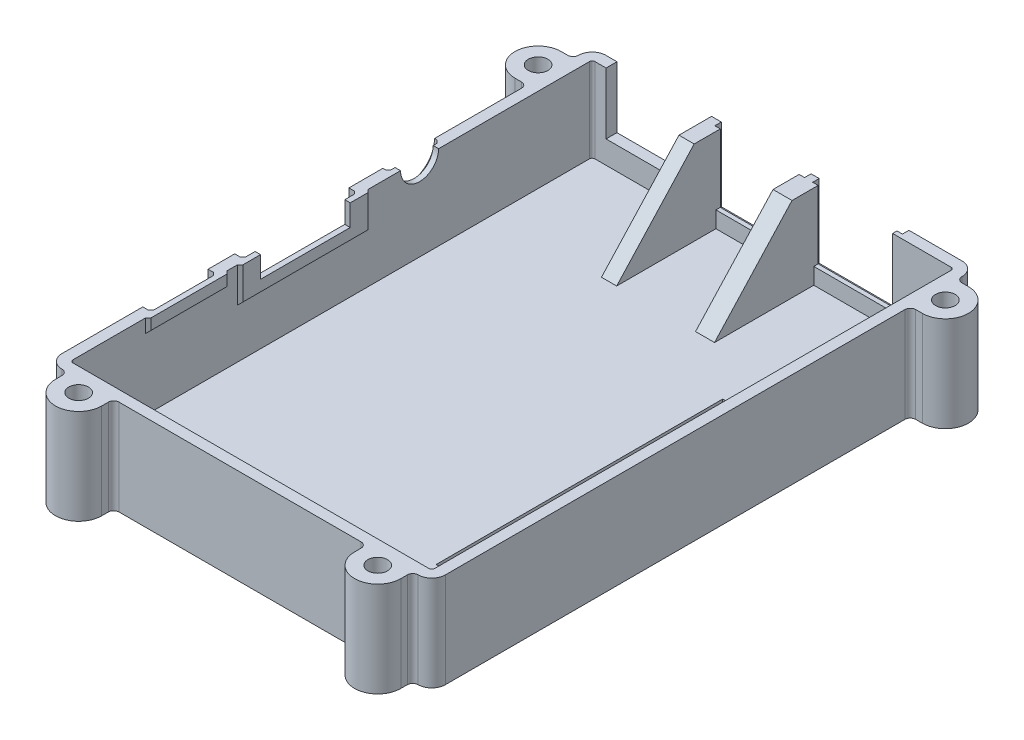
SolidWorks part; units mm, degrees
ref_plane "Front Plane" through (0, 0, 0) normal (0, 0, 1) x (1, 0, 0)
ref_plane "Top Plane" through (0, 0, 0) normal (0, 1, 0) x (1, 0, 0)
ref_plane "Right Plane" through (0, 0, 0) normal (1, 0, 0) x (0, 0, -1)
sketch "Sketch2" plane through (0, 0, 0) normal (0, 1, 0) x (1, 0, 0)
  line L1 (2.5, 0) -> (68, 0)
  line L2 (0, 2.5) -> (0, 97.5)
  line L3 (2.5, 100) -> (68, 100)
  line L4 (70.5, 2.5) -> (70.5, 97.5)
  arc A0 (0, 2.5) -> (2.5, 0) centre (2.5, 2.5) ccw
  arc A1 (68, 0) -> (70.5, 2.5) centre (68, 2.5) ccw
  arc A2 (70.5, 97.5) -> (68, 100) centre (68, 97.5) ccw
  arc A3 (2.5, 100) -> (0, 97.5) centre (2.5, 97.5) ccw
  point P7 (0, 0)
  point P10 (70.5, 0)
  point P13 (70.5, 100)
  point P16 (0, 100)
  dimension "D3" = 2.5
  dimension "D1" = 70.5
  dimension "D2" = 100
extrude "Base" add sketch "Sketch2" along normal blind 17.5
shell "Shell" thickness 2 removed face at (35.25, 17.5, -50)
sketch "Sketch14" plane through (0, 0, 0) normal (0, -1, 0) x (1, 0, 0)
  line L0 (35.25, 0) -> (35.25, -100) construction
  line L2 (68, -100) -> (2.5, -100) construction
  line L3 (-2.2, -88) -> (0, -88)
  line L4 (0, -97.5) -> (0, -2.5) construction
  line L5 (0, -88) -> (0, -96.5)
  line L6 (0, -96.5) -> (-2.2, -96.5)
  line L7 (3.5, 2.2) -> (3.5, 0)
  line L8 (2.5, 0) -> (68, 0) construction
  line L9 (3.5, 0) -> (12, 0)
  line L10 (12, 0) -> (12, 2.2)
  line L11 (72.7, -88) -> (70.5, -88)
  line L12 (70.5, -96.5) -> (72.7, -96.5)
  line L13 (70.5, -88) -> (70.5, -96.5)
  line L14 (58.5, 0) -> (58.5, 2.2)
  line L15 (67, 0) -> (58.5, 0)
  line L16 (67, 2.2) -> (67, 0)
  line L17 (2.5, 0) -> (68, 0) construction
  arc A0 (-2.2, -88) -> (-2.2, -96.5) centre (-2.2, -92.25) ccw
  arc A1 (3.5, 2.2) -> (12, 2.2) centre (7.75, 2.2) cw
  arc A2 (72.7, -88) -> (72.7, -96.5) centre (72.7, -92.25) cw
  arc A3 (67, 2.2) -> (58.5, 2.2) centre (62.75, 2.2) ccw
  dimension "D1" = 2.2
  dimension "D2" = 8.5
  dimension "D3" = 3.5
  dimension "D4" = 3.5
extrude "Clamps" add sketch "Sketch14" against normal up to surface (17.5 mm away) up to face at (35.25, 17.5, -50)
fillet "Clamp Fillets" radius 1 8 edges at (58.5, 8.75, 0) (67, 8.75, 0) (12, 8.75, 0) (3.5, 8.75, 0) (0, 8.75, -96.5) (0, 8.75, -88) (70.5, 8.75, -88) (70.5, 8.75, -96.5)
sketch "Sketch20" plane through (0, 0, 0) normal (0, -1, 0) x (1, 0, 0)
  circle A0 centre (7.75, 2.2) radius 1.8
  circle A1 centre (62.75, 2.2) radius 1.8
  circle A2 centre (72.7, -92.25) radius 1.8
  circle A3 centre (-2.2, -92.25) radius 1.8
  arc A4 (12, 2.2) -> (3.5, 2.2) centre (7.75, 2.2) ccw construction
  arc A5 (67, 2.2) -> (58.5, 2.2) centre (62.75, 2.2) ccw construction
  arc A6 (-2.2, -88) -> (-2.2, -96.5) centre (-2.2, -92.25) ccw construction
  arc A7 (72.7, -96.5) -> (72.7, -88) centre (72.7, -92.25) ccw construction
  dimension "D1" = 3.6
extrude "Clamp Holes" cut sketch "Sketch20" against normal through all
sketch "Sketch21" plane through (0, 0, 0) normal (0, -1, 0) x (1, 0, 0)
  circle A0 centre (7.75, 2.2) radius 2.9
  circle A1 centre (62.75, 2.2) radius 2.9
  circle A2 centre (72.7, -92.25) radius 2.9
  circle A3 centre (-2.2, -92.25) radius 2.9
  circle A4 centre (-2.2, -92.25) radius 1.8 construction
  circle A5 centre (7.75, 2.2) radius 1.8 construction
  circle A6 centre (62.75, 2.2) radius 1.8 construction
  circle A7 centre (72.7, -92.25) radius 1.8 construction
  dimension "D1" = 5.8
extrude "Clamp Countersinks" cut sketch "Sketch21" against normal blind 3.4
chamfer "Clamp Countersink Chamfers" distance 0.3 angle 45 4 edges at (-2.2, 0, -95.15) (72.7, 0, -95.15) (62.75, 0, -0.7) (7.75, 0, -0.7)
sketch "Sketch24" plane through (0, 0, -100) normal (0, 0, -1) x (-1, 0, 0)
  line L0 (-68, 17.5) -> (-2.5, 17.5) construction
  line L1 (-57.25, 17.5) -> (-42.75, 17.5)
  line L2 (-57.25, 17.5) -> (-57.25, 5)
  line L3 (-57.25, 5) -> (-42.75, 5)
  line L4 (-42.75, 17.5) -> (-42.75, 5)
  line L6 (0, 17.5) -> (0, 0) construction
  line L7 (-39.25, 17.5) -> (-24.75, 17.5)
  line L8 (-39.25, 17.5) -> (-39.25, 5)
  line L9 (-39.25, 5) -> (-24.75, 5)
  line L10 (-24.75, 17.5) -> (-24.75, 5)
  dimension "D1" = 14.5
  dimension "D2" = 24.75
  dimension "D3" = 42.75
  dimension "D4" = 12.5
extrude "USB Cutout" cut sketch "Sketch24" against normal blind 18.25
sketch "Sketch25" plane through (0, 0, -100) normal (0, 0, -1) x (-1, 0, 0)
  line L0 (-42.75, 17.5) -> (-39.25, 17.5) construction
  line L1 (-41.75, 17.5) -> (-58.25, 17.5)
  line L2 (-41.75, 17.5) -> (-41.75, 4)
  line L3 (-41.75, 4) -> (-58.25, 4)
  line L4 (-58.25, 17.5) -> (-58.25, 4)
  line L6 (-24.75, 17.5) -> (-2.5, 17.5) construction
  line L7 (-23.75, 17.5) -> (-40.25, 17.5)
  line L8 (-23.75, 17.5) -> (-23.75, 4)
  line L9 (-23.75, 4) -> (-40.25, 4)
  line L10 (-40.25, 17.5) -> (-40.25, 4)
  line L12 (-57.25, 17.5) -> (-57.25, 5) construction
  line L13 (-42.75, 5) -> (-42.75, 17.5) construction
  line L14 (-39.25, 17.5) -> (-39.25, 5) construction
  line L15 (-24.75, 5) -> (-24.75, 17.5) construction
  point P18 (-57.25, 11.25)
  dimension "D1" = 1
  dimension "D2" = 1
  dimension "D3" = 1
  dimension "D4" = 1
  dimension "D5" = 13.5
extrude "USB Approach" cut sketch "Sketch25" against normal blind 1.2
sketch "Sketch26" plane through (42.75, 0, 0) normal (1, 0, 0) x (0, 0, -1)
  line L0 (98, 2) -> (98, 17.5)
  line L1 (98, 17.5) -> (94, 17.5)
  line L2 (98, 2) -> (79.75, 2)
  line L3 (79.75, 2) -> (94, 17.5)
  line L4 (100, 4) -> (100, 17.5) construction
  line L5 (98.8, 5) -> (98.8, 17.5) construction
  dimension "D1" = 6
  dimension "D2" = 19.05
extrude "USB Inner Support" add sketch "Sketch26" against normal up to surface (3.5 mm away) up to face at (39.25, 11.25, -98.4)
sketch "Sketch27" plane through (24.75, 0, 0) normal (1, 0, 0) x (0, 0, -1)
  line L0 (98, 2) -> (98, 17.5)
  line L1 (98, 17.5) -> (94, 17.5)
  line L2 (98, 2) -> (79.75, 2)
  line L3 (79.75, 2) -> (94, 17.5)
  line L4 (100, 4) -> (100, 17.5) construction
  line L5 (98.8, 5) -> (98.8, 17.5) construction
  dimension "D1" = 6
  dimension "D2" = 19.05
extrude "USB Outer Support" add sketch "Sketch27" against normal blind 2.8
sketch "Sketch28" plane through (0, 0, -100) normal (0, 0, -1) x (-1, 0, 0)
  line L0 (-23.75, 17.5) -> (-2.5, 17.5) construction
  line L1 (-21.95, 17.5) -> (-4.55, 17.5)
  line L2 (-21.95, 17.5) -> (-21.95, 6.2)
  line L3 (-21.95, 6.2) -> (-4.55, 6.2)
  line L4 (-4.55, 17.5) -> (-4.55, 6.2)
  line L5 (0, 17.5) -> (0, 0) construction
  dimension "D1" = 17.4
  dimension "D2" = 4.55
  dimension "D3" = 11.3
extrude "RJ45 Cutout" cut sketch "Sketch28" against normal blind 22.7
sketch "Sketch29" plane through (2, 0, 0) normal (1, 0, 0) x (0, 0, -1)
  line L0 (97.5, 17.5) -> (2.5, 17.5) construction
  line L1 (15.85, 17.5) -> (30.85, 17.5)
  line L2 (15.85, 17.5) -> (15.85, 15)
  line L3 (15.85, 15) -> (30.85, 15)
  line L4 (30.85, 17.5) -> (30.85, 15)
  line L5 (0, 17.5) -> (0, 0) construction
  line L6 (32.75, 17.5) -> (56.75, 17.5)
  line L7 (32.75, 17.5) -> (32.75, 11.07)
  line L8 (32.75, 11.07) -> (56.75, 11.07)
  line L9 (56.75, 17.5) -> (56.75, 11.07)
  dimension "D1" = 24
  dimension "D2" = 15
  dimension "D3" = 15.85
  dimension "D4" = 32.75
  dimension "D5" = 2.5
  dimension "D6" = 6.43
extrude "HDMI Support" add sketch "Sketch29" along normal blind 0.5
chamfer "HDMI Support Chamfer" distance 0.5 angle 45 6 edges at (2.5, 14.285, -56.75) (2.5, 11.07, -44.75) (2.5, 14.285, -32.75) (2.5, 16.25, -30.85) (2.5, 15, -23.35) (2.5, 16.25, -15.85)
sketch "Sketch30" plane through (0, 0, 0) normal (-1, 0, 0) x (0, 0, 1)
  line L0 (-87, 17.5) -> (-2.5, 17.5) construction
  line L1 (-34.25, 17.5) -> (-55.25, 17.5)
  line L2 (-34.25, 17.5) -> (-34.25, 11.57)
  line L3 (-34.25, 11.57) -> (-55.25, 11.57)
  line L4 (-55.25, 17.5) -> (-55.25, 11.57)
  line L5 (0, 17.5) -> (0, 0) construction
  line L6 (-29.35, 17.5) -> (-17.35, 17.5)
  line L7 (-29.35, 17.5) -> (-29.35, 15.5)
  line L8 (-29.35, 15.5) -> (-17.35, 15.5)
  line L9 (-17.35, 17.5) -> (-17.35, 15.5)
  dimension "D1" = 12
  dimension "D2" = 21
  dimension "D3" = 17.35
  dimension "D4" = 34.25
  dimension "D5" = 5.93
  dimension "D6" = 2
extrude "HDMI Approach" cut sketch "Sketch30" against normal blind 1.5
sketch "Sketch31" plane through (1.5, 0, 0) normal (-1, 0, 0) x (0, 0, 1)
  line L0 (-34.25, 17.5) -> (-55.25, 17.5) construction
  line L1 (-53, 17.5) -> (-36.5, 17.5)
  line L2 (-53, 17.5) -> (-53, 13.57)
  line L3 (-53, 13.57) -> (-36.5, 13.57)
  line L4 (-36.5, 17.5) -> (-36.5, 13.57)
  line L5 (-55.25, 17.5) -> (-55.25, 11.57) construction
  line L6 (-34.25, 11.57) -> (-34.25, 17.5) construction
  line L7 (-55.25, 11.57) -> (-34.25, 11.57) construction
  dimension "D1" = 2.25
  dimension "D2" = 2.25
  dimension "D3" = 2
extrude "HDMI Cutout" cut sketch "Sketch31" against normal blind 1
chamfer "HDMI Approach Chamfer" distance 0.5 angle 45 6 edges at (1.5, 16.5, -17.35) (1.5, 15.5, -23.35) (1.5, 16.5, -29.35) (1.5, 14.535, -34.25) (1.5, 11.57, -44.75) (1.5, 14.535, -55.25)
sketch "Sketch32" plane through (0, 0, 0) normal (-1, 0, 0) x (0, 0, 1)
  line L0 (-87, 17.5) -> (-55.25, 17.5) construction
  line L1 (0, 17.5) -> (0, 0) construction
  circle A0 centre (-66.25, 17.5) radius 3.5
  dimension "D1" = 7
  dimension "D2" = 66.25
extrude "Audio Cutout" cut sketch "Sketch32" against normal blind 2
sketch "Sketch33" plane through (0, 0, 0) normal (-1, 0, 0) x (0, 0, 1)
  circle A0 centre (-66.25, 17.5) radius 4.75
  arc A1 (-69.75, 17.5) -> (-62.75, 17.5) centre (-66.25, 17.5) ccw construction
  dimension "D1" = 9.5
extrude "Audio Approach" cut sketch "Sketch33" against normal blind 1
chamfer "Audio Approach Chamfer" distance 0.5 angle 45 1 edges at (1, 12.75, -66.25)
sketch "Sketch34" plane through (0, 0, 0) normal (0, -1, 0) x (1, 0, 0)
  line L0 (70.5, -2.5) -> (70.5, -87) construction
  line L1 (52.5, -18.8) -> (58.5, -18.8)
  line L2 (52.5, -18.8) -> (52.5, -71.5)
  line L3 (52.5, -71.5) -> (58.5, -71.5)
  line L4 (58.5, -18.8) -> (58.5, -71.5)
  line L5 (13, 0) -> (57.5, 0) construction
  point P6 (55.5, -18.8)
  dimension "D1" = 6
  dimension "D2" = 52.7
  dimension "D3" = 12
  dimension "D4" = 18.8
extrude "Header Cutout" cut sketch "Sketch34" against normal blind 2
sketch "Sketch35" plane through (0, 0, 0) normal (0, -1, 0) x (1, 0, 0)
  line L0 (55.5, -18.8) -> (55.5, -71.5) construction
  line L1 (58.5, -18.8) -> (52.5, -18.8) construction
  line L2 (52.5, -71.5) -> (58.5, -71.5) construction
  line L3 (52.5, -45.15) -> (58.5, -45.15) construction
  line L4 (52.5, -18.8) -> (52.5, -71.5) construction
  line L5 (58.5, -71.5) -> (58.5, -18.8) construction
  line L6 (56, -18.8) -> (55, -18.8)
  line L7 (55, -18.8) -> (55, -19.8)
  line L8 (55, -19.8) -> (53.5, -19.8)
  line L9 (53.5, -19.8) -> (53.5, -24.7625)
  line L10 (53.5, -24.7625) -> (52.5, -24.7625)
  line L11 (52.5, -24.7625) -> (52.5, -25.7625)
  line L12 (52.5, -25.7625) -> (53.5, -25.7625)
  line L13 (53.5, -25.7625) -> (53.5, -37.6875)
  line L14 (53.5, -37.6875) -> (52.5, -37.6875)
  line L15 (52.5, -37.6875) -> (52.5, -38.6875)
  line L16 (52.5, -38.6875) -> (53.5, -38.6875)
  line L17 (53.5, -38.6875) -> (53.5, -43.65)
  line L18 (53.5, -43.65) -> (55, -43.65)
  line L19 (55, -43.65) -> (55, -44.65)
  line L20 (55, -44.65) -> (52.5, -44.65)
  line L21 (52.5, -44.65) -> (52.5, -45.65)
  line L22 (56, -71.5) -> (55, -71.5)
  line L23 (55, -45.65) -> (52.5, -45.65)
  line L24 (55, -46.65) -> (55, -45.65)
  line L25 (53.5, -46.65) -> (55, -46.65)
  line L26 (53.5, -51.6125) -> (53.5, -46.65)
  line L27 (52.5, -51.6125) -> (53.5, -51.6125)
  line L28 (52.5, -52.6125) -> (52.5, -51.6125)
  line L29 (53.5, -52.6125) -> (52.5, -52.6125)
  line L30 (53.5, -64.5375) -> (53.5, -52.6125)
  line L31 (52.5, -64.5375) -> (53.5, -64.5375)
  line L32 (52.5, -65.5375) -> (52.5, -64.5375)
  line L33 (53.5, -65.5375) -> (52.5, -65.5375)
  line L34 (53.5, -70.5) -> (53.5, -65.5375)
  line L35 (55, -70.5) -> (53.5, -70.5)
  line L36 (55, -71.5) -> (55, -70.5)
  line L37 (56, -71.5) -> (56, -70.5)
  line L38 (56, -70.5) -> (57.5, -70.5)
  line L39 (57.5, -70.5) -> (57.5, -65.5375)
  line L40 (57.5, -65.5375) -> (58.5, -65.5375)
  line L41 (58.5, -65.5375) -> (58.5, -64.5375)
  line L42 (58.5, -64.5375) -> (57.5, -64.5375)
  line L43 (57.5, -64.5375) -> (57.5, -52.6125)
  line L44 (57.5, -52.6125) -> (58.5, -52.6125)
  line L45 (58.5, -52.6125) -> (58.5, -51.6125)
  line L46 (58.5, -51.6125) -> (57.5, -51.6125)
  line L47 (57.5, -51.6125) -> (57.5, -46.65)
  line L48 (57.5, -46.65) -> (56, -46.65)
  line L49 (56, -46.65) -> (56, -45.65)
  line L50 (56, -45.65) -> (58.5, -45.65)
  line L51 (58.5, -44.65) -> (58.5, -45.65)
  line L52 (56, -44.65) -> (58.5, -44.65)
  line L53 (56, -43.65) -> (56, -44.65)
  line L54 (57.5, -43.65) -> (56, -43.65)
  line L55 (57.5, -38.6875) -> (57.5, -43.65)
  line L56 (58.5, -38.6875) -> (57.5, -38.6875)
  line L57 (58.5, -37.6875) -> (58.5, -38.6875)
  line L58 (57.5, -37.6875) -> (58.5, -37.6875)
  line L59 (57.5, -25.7625) -> (57.5, -37.6875)
  line L60 (58.5, -25.7625) -> (57.5, -25.7625)
  line L61 (58.5, -24.7625) -> (58.5, -25.7625)
  line L62 (57.5, -24.7625) -> (58.5, -24.7625)
  line L63 (57.5, -19.8) -> (57.5, -24.7625)
  line L64 (56, -19.8) -> (57.5, -19.8)
  line L65 (56, -18.8) -> (56, -19.8)
  dimension "D1" = 0.5
  dimension "D2" = 1
  dimension "D3" = 1.5
  dimension "D4" = 11.925
extrude "Header Cover" add sketch "Sketch35" against normal blind 1
